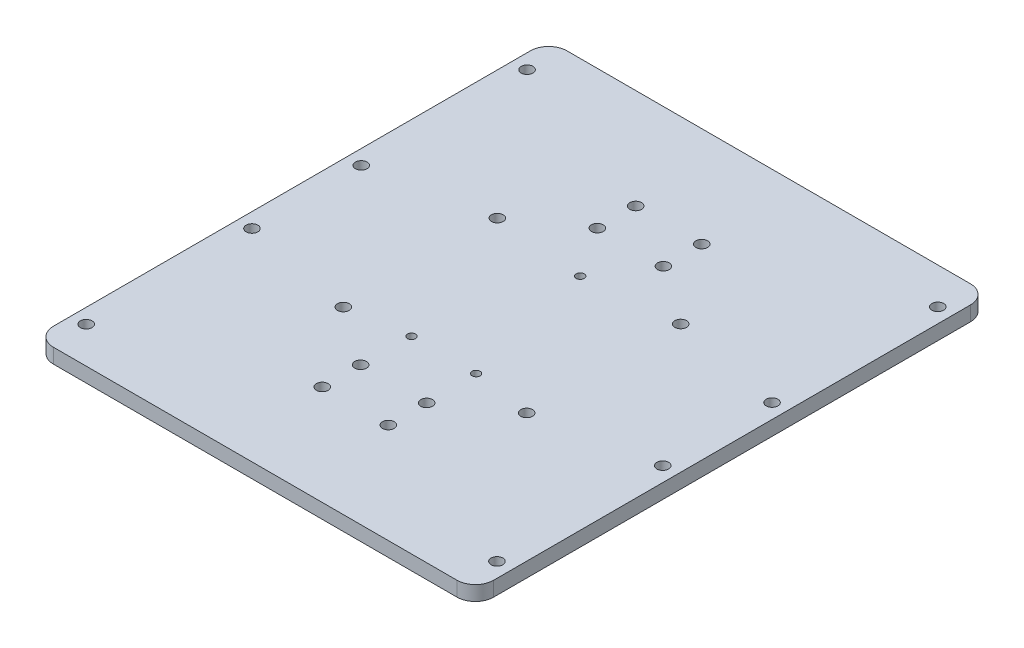
SolidWorks part; units mm, degrees
material "自定义塑料"
ref_plane "前视基准面" through (0, 0, 0) normal (0, 0, 1) x (1, 0, 0)
ref_plane "上视基准面" through (0, 0, 0) normal (0, 1, 0) x (1, 0, 0)
ref_plane "右视基准面" through (0, 0, 0) normal (1, 0, 0) x (0, 0, -1)
sketch "草图1" plane through (0, 0, 0) normal (0, 1, 0) x (1, 0, 0)
  line L0 (0, 0) -> (-20.2314, 0) construction
  line L1 (-60, 70) -> (60, 70)
  line L2 (-60, 70) -> (-60, -70)
  line L3 (-60, -70) -> (60, -70)
  line L4 (60, 70) -> (60, -70)
  line L5 (-60, 70) -> (60, -70) construction
  line L6 (-60, -70) -> (60, 70) construction
  line L7 (0, 0) -> (0, 21.0425) construction
  line L8 (-60, 37.5) -> (-53.3899, 37.5) construction
  circle A0 centre (-56, 60.1) radius 1.6
  circle A1 centre (-56, 14.9) radius 1.6
  circle A2 centre (-9, 42.73) radius 1.6
  circle A3 centre (-9, 32.27) radius 1.6
  circle A4 centre (-56, -14.9) radius 1.6
  circle A5 centre (-9, -32.27) radius 1.6
  circle A6 centre (-9, -42.73) radius 1.6
  circle A7 centre (-56, -60.1) radius 1.6
  circle A8 centre (56, -60.1) radius 1.6
  circle A9 centre (9, -42.73) radius 1.6
  circle A10 centre (9, -32.27) radius 1.6
  circle A11 centre (56, -14.9) radius 1.6
  circle A12 centre (56, 14.9) radius 1.6
  circle A13 centre (9, 32.27) radius 1.6
  circle A14 centre (9, 42.73) radius 1.6
  circle A15 centre (56, 60.1) radius 1.6
  circle A16 centre (0, 18.6) radius 1.1
  circle A17 centre (8.8, -18.6) radius 1.1
  circle A18 centre (-8.8, -18.6) radius 1.1
  circle A19 centre (-25, 21) radius 1.6
  circle A20 centre (25, 21) radius 1.6
  circle A21 centre (25, -21) radius 1.6
  circle A22 centre (-25, -21) radius 1.6
  point P0 (0, 0)
  dimension "D4" = 3.2
  dimension "D9" = 2.2
  dimension "D15" = 3.2
  dimension "D1" = 120
  dimension "D2" = 140
  dimension "D3" = 37.5
  dimension "D5" = 45.2
  dimension "D6" = 4
  dimension "D7" = 10.46
  dimension "D8" = 47
  dimension "D10" = 18.6
  dimension "D11" = 18.6
  dimension "D12" = 8.8
  dimension "D13" = 50
  dimension "D14" = 42
extrude "凸台-拉伸1" add sketch "草图1" along normal blind 4
fillet "圆角1" radius 5 4 edges at (-60, 2, -70) (60, 2, -70) (60, 2, 70) (-60, 2, 70)
